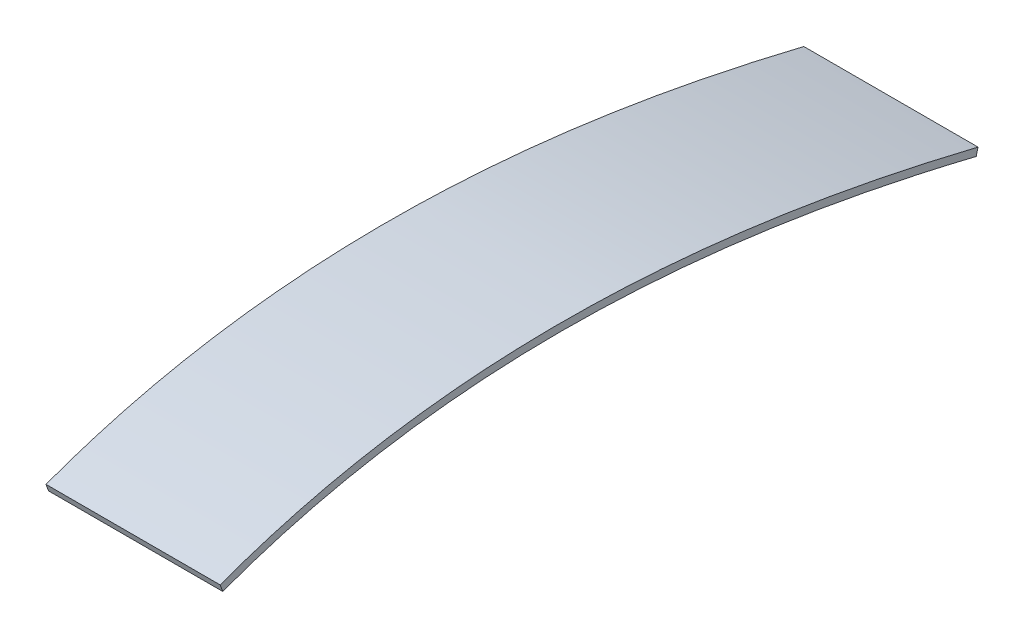
SolidWorks part; units mm, degrees
ref_plane "Front Plane" through (0, 0, 0) normal (0, 0, 1) x (1, 0, 0)
ref_plane "Top Plane" through (0, 0, 0) normal (0, 1, 0) x (1, 0, 0)
ref_plane "Right Plane" through (0, 0, 0) normal (1, 0, 0) x (0, 0, -1)
sketch "Sketch2" plane through (0, 0, 0) normal (1, 0, 0) x (0, 0, -1)
  line L0 (628.1543, 1334.841) -> (635.2765, 1363.9833)
  line L1 (-2400.3471, 1334.841) -> (-2410.7903, 1362.9646)
  spline S0 degree 3 poles (628.1543, 1334.841) (-348.2547, 1573.4666) (-1437.4882, 1692.3838) (-2400.3471, 1334.841) knots 0 0 0 0 1 1 1 1
  spline S1 degree 1 poles (635.2765, 1363.9833) (-2410.7903, 1362.9646) knots 0 0 1 1 construction
  spline S2 degree 3 poles (635.2765, 1363.9833) (619.9574, 1367.7271) (589.3304, 1375.14) (543.1723, 1386.0892) (496.8707, 1396.8434) (434.9268, 1410.9172) (357.1308, 1427.9893) (263.2298, 1447.5786) (168.8274, 1466.2048) (42.3463, 1489.6678) (-116.7924, 1516.2599) (-309.0719, 1543.2647) (-566.7335, 1572.0264) (-890.3608, 1593.0734) (-1213.7424, 1590.7116) (-1470.9045, 1572.6453) (-1662.6524, 1550.4725) (-1852.9229, 1519.1414) (-2009.9525, 1484.9541) (-2134.4788, 1452.4897) (-2227.2776, 1425.518) (-2304.0815, 1400.7976) (-2365.1704, 1379.6469) (-2395.617, 1368.599) (-2410.7903, 1362.9646) knots 0 0 0 0 0.015625 0.03125 0.046875 0.0625 0.09375 0.125 0.15625 0.1875 0.25 0.3125 0.375 0.5 0.625 0.6875 0.75 0.8125 0.875 0.90625 0.9375 0.96875 0.984375 1 1 1 1
  dimension "D1" = 30
extrude "Boss-Extrude1" add sketch "Sketch2" along normal blind 350 and the other way blind 350
